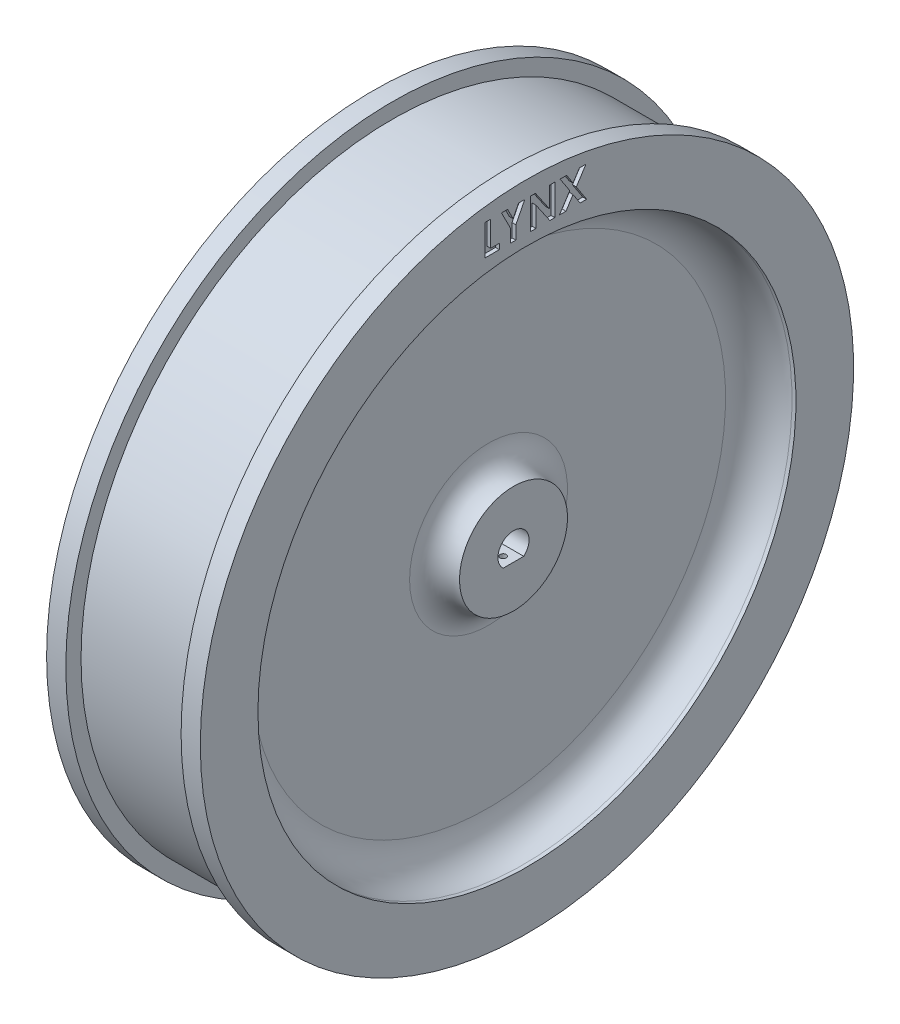
SolidWorks part; units mm, degrees
ref_plane "Front Plane" through (0, 0, 0) normal (0, 0, 1) x (1, 0, 0)
ref_plane "Top Plane" through (0, 0, 0) normal (0, 1, 0) x (1, 0, 0)
ref_plane "Right Plane" through (0, 0, 0) normal (1, 0, 0) x (0, 0, -1)
sketch "Sketch1" plane through (0, 0, 0) normal (0, 0, 1) x (1, 0, 0)
  line L1 (8.9739, 70) -> (10, 70)
  line L2 (10, 70) -> (10, 85)
  line L3 (10, 85) -> (5, 85)
  line L5 (5, 81.0389) -> (-25, 81.0389)
  line L7 (-25, 85) -> (-30, 85)
  line L8 (-30, 85) -> (-30, 70)
  line L9 (-30, 70) -> (-15, 70) construction
  line L10 (-15, 70) -> (-15, 0) construction
  line L12 (0, 0) -> (32.5586, 0) construction
  line L13 (0, 0) -> (0, 98.1963) construction
  line L14 (5, 81.0389) -> (5, 85)
  line L15 (-25, 81.0389) -> (-25, 85)
  line L16 (0, 61.6845) -> (0, 20.54)
  line L17 (6.49, 14.05) -> (6.5, 14.05)
  line L18 (6.5, 14.05) -> (6.5, 4.05)
  line L19 (6.5, 4.05) -> (-9.5, 4.05)
  line L20 (-9.5, 4.05) -> (-9.5, 0)
  line L21 (-9.5, 0) -> (-15, 0)
  line L22 (-15, 0) -> (-15, 10)
  arc A0 (0, 61.6845) -> (8.9739, 70) centre (8.9739, 61) cw
  arc A1 (0, 20.54) -> (6.49, 14.05) centre (6.49, 20.54) ccw
  conic Q0 (-30, 70) -> (-15, 10) control (-18.6357, 58.0621) rho 0.697214
  point P15 (0, 70)
  point P27 (0, 14.05)
  dimension "D1" = 5
  dimension "D2" = 5
  dimension "D11" = 9
  dimension "D16" = 6.49
  dimension "D3" = 30
  dimension "D4" = 15
  dimension "D5" = 15
  dimension "D6" = 10
  dimension "D7" = 10
  dimension "D8" = 15
  dimension "D9" = 4.05
  dimension "D10" = 70
  dimension "D12" = 16
  dimension "D13" = 10
  dimension "D14" = 3.5
  dimension "D15" = 5.5
revolve "Revolve2" add sketch "Sketch1" angle 360 about L12
sketch "Sketch2" plane through (6.5, 0, 0) normal (1, 0, 0) x (0, 0, -1)
  line L0 (0, -3.05) -> (-2.6646, -3.05)
  line L1 (0, -3.05) -> (2.6646, -3.05)
  circle A1 centre (0, 0) radius 4.05 construction
  circle A2 centre (0, 0) radius 4.05 construction
  arc A3 (2.6646, -3.05) -> (-2.6646, -3.05) centre (0, 0) cw
extrude "Boss-Extrude2" add sketch "Sketch2" against normal blind 16
sketch "Sketch5" plane through (10, 0, 0) normal (1, 0, 0) x (0, 0, -1)
  text T0 "LYNX" font "Century Gothic" height 8
extrude "Cut-Extrude2" cut sketch "Sketch5" against normal blind 1
sketch "Sketch6" plane through (0, -3.05, 0) normal (0, 1, 0) x (1, 0, 0)
  line L0 (6.5, -2.6646) -> (6.5, 2.6646) construction
  line L2 (6.5, 0) -> (1.9421, 0) construction
  circle A0 centre (3.806, 0) radius 0.8
extrude "Cut-Extrude4" cut sketch "Sketch6" against normal blind 20
ref_axis "Axis1" through (21.4475, 0, 0) along (-1, 0, 0)
